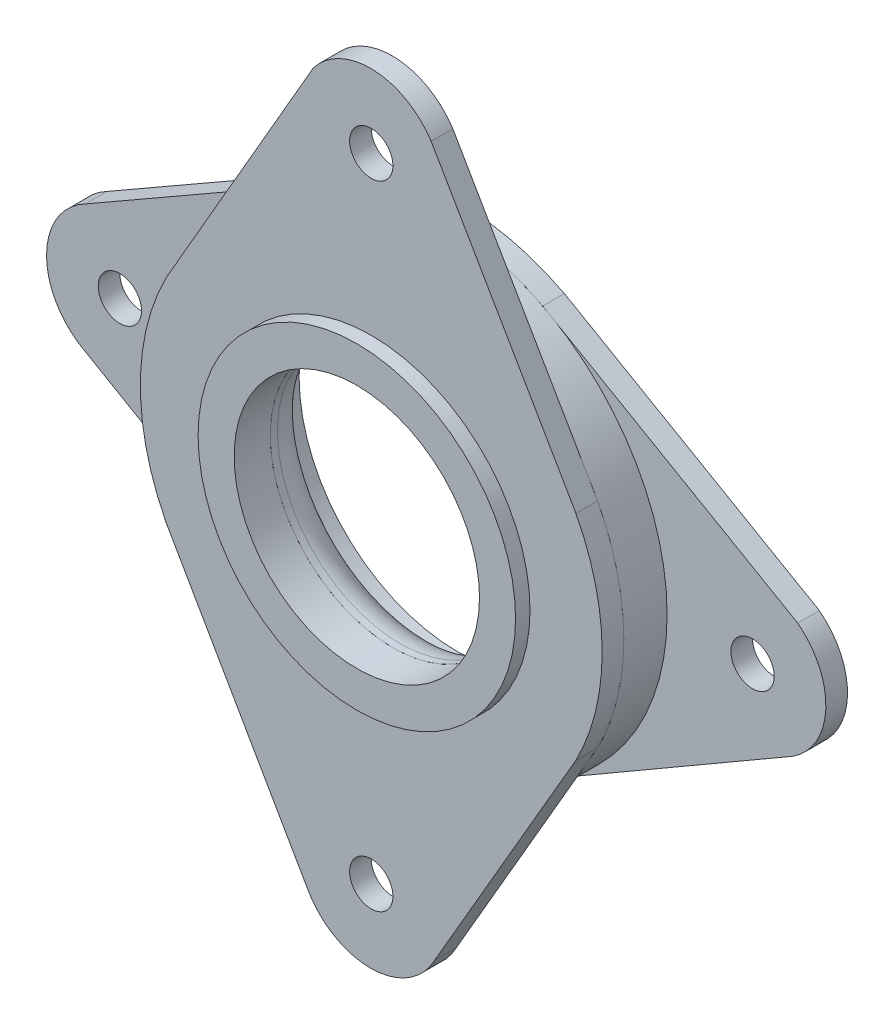
SolidWorks part; units mm, degrees
other "Markup1"
sketch "Sketch7" plane through (27, -27, 7) normal (0.0115, -0.0317, 0.9994) x (0.6877, 0.7259, 0.0151)
material "ABS"
ref_plane "Front Plane" through (0, 0, 0) normal (0, 0, 1) x (1, 0, 0)
ref_plane "Top Plane" through (0, 0, 0) normal (0, 1, 0) x (1, 0, 0)
ref_plane "Right Plane" through (0, 0, 0) normal (1, 0, 0) x (0, 0, -1)
sketch "Sketch1" plane through (0, 0, 0) normal (0, 0, 1) x (1, 0, 0)
  line L1 (7.3794, 14.1966) -> (25.0466, 4.0094)
  line L2 (-24.3098, 4.4793) -> (-7.325, 14.2248)
  line L3 (-24.3029, -4.3932) -> (-7.4267, -14.1719)
  line L4 (7.408, -14.1817) -> (24.7169, -4.1525)
  line L7 (20.4006, 0) -> (41.1933, 0) construction
  arc A0 (-7.4267, -14.1719) -> (7.408, -14.1817) centre (0, 0) ccw construction
  circle A1 centre (0, 0) radius 27 construction
  arc A4 (24.7169, -4.1525) -> (25.0466, 4.0094) centre (22, 0.0449) ccw
  arc A5 (-7.4267, -14.1719) -> (7.408, -14.1817) centre (0, 0) ccw
  arc A6 (-24.3098, 4.4793) -> (-24.3029, -4.3932) centre (-22, 0.0449) ccw
  arc A7 (7.3794, 14.1966) -> (-7.325, 14.2248) centre (0, 0) ccw construction
  arc A8 (7.3794, 14.1966) -> (-7.325, 14.2248) centre (0, 0) ccw
  point P7 (0, 0)
  dimension "D1" = 32
  dimension "D2" = 54
  dimension "D7" = 10
  dimension "D6" = 22
extrude "Boss-Extrude1" add sketch "Sketch1" along normal blind 1.5
sketch "Sketch2" plane through (0, 0, 1.5) normal (0, 0, 1) x (1, 0, 0)
  line L0 (31.1876, 0) -> (-31.1876, 0) construction
  circle A0 centre (-21.92, 0) radius 1.5
  circle A1 centre (21.92, 0) radius 1.5
  circle A2 centre (0, 0) radius 8.5
  point P9 (0, 0)
  dimension "D1" = 17
  dimension "D2" = 3
  dimension "D3" = 3
  dimension "D4" = 21.92
  dimension "D5" = 21.92
extrude "Cut-Extrude1" cut sketch "Sketch2" against normal through all
ref_plane "Plane1" through (0, 0, 3) normal (0, 0, 1) x (1, 0, 0)
mirror "Mirror2" about plane through (0, 0, 3) normal (0, 0, 1) of bodies 102
move or copy body "Body-Move/Copy1" bodies to move or copy 104 copy no rotation origin (0, 0, 0) rotation axis (0, 0, 1) rotation angle 90
sketch "Sketch3" plane through (0, 0, 3) normal (0, 0, 1) x (1, 0, 0)
  circle A0 centre (0, 0) radius 16
  circle A1 centre (0, 0) radius 8.5
  dimension "D1" = 32
extrude "Boss-Extrude2" add sketch "Sketch3" along normal blind 1.5 and the other way blind 1.5 separate body
sketch "Sketch4" plane through (0, 0, 0) normal (0, 0, -1) x (-1, 0, 0)
  circle A0 centre (0, 0) radius 11
  dimension "D1" = 22
extrude "Cut-Extrude2" cut sketch "Sketch4" against normal up to surface (1.5 mm away) up to face at (-20.42, 0, 1.5)
fillet "Fillet1" radius 2.5 1 edges at (8.5, 0, 1.5)
sketch "Sketch6" plane through (0, 0, 6) normal (0, 0, 1) x (1, 0, 0)
  circle A0 centre (0, 0) radius 8.5
  circle A1 centre (0, 0) radius 11
  dimension "D1" = 22
  dimension "D2" = 17
extrude "Boss-Extrude4" add sketch "Sketch6" along normal blind 1
